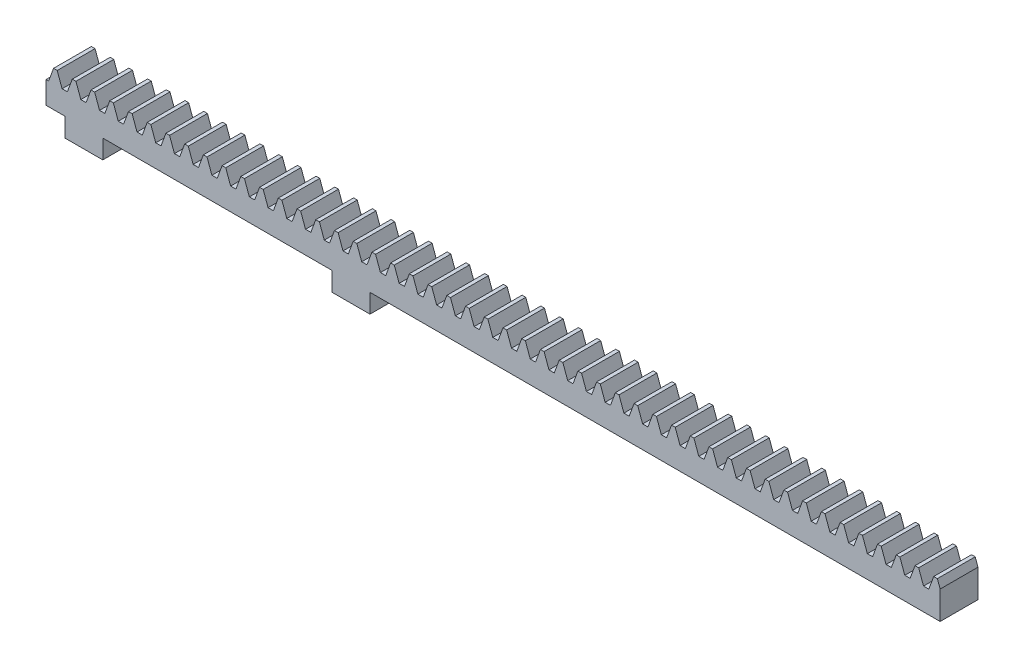
SolidWorks part; units mm, degrees
ref_plane "Plane1" through (0, 0, 0) normal (0, 0, 1) x (1, 0, 0)
ref_plane "Plane2" through (0, 0, 0) normal (0, 1, 0) x (1, 0, 0)
ref_plane "Plane3" through (0, 0, 0) normal (1, 0, 0) x (0, 0, -1)
sketch "HoldingSke" plane through (0, 0, 0) normal (0, 1, 0) x (1, 0, 0)
  line L0 (0, 0) -> (0.1392, 0.9903)
  line L1 (-15, 0) -> (100, 0) construction
  line L2 (0, 0) -> (-2.1039, 2.3779)
  line L3 (0, 0) -> (-11.863, 4.5341)
  line L4 (0, 0) -> (5.6657, 6.5177)
  line L5 (0, 0) -> (-23.7986, -8.8762)
  line L6 (0, 0) -> (-10.5278, -7.1032)
  line L9 (-71.009, 38.7566) -> (69.9449, 90.0596)
  line L10 (-76.2, 3.3779) -> (-71.2, 3.3779)
  line L11 (0, 0) -> (-6.35, 0)
  line L12 (-76.2, 101.6) -> (-76.162, 101.6)
  line L13 (24.9733, 27.94) -> (52.9518, 28.4284)
  line L14 (24.9733, 27.94) -> (24.9743, 27.94)
  line L15 (24.9733, 27.94) -> (100.4006, 29.5858)
  circle A0 centre (0, 0) radius 19.05
  circle A1 centre (0, 0) radius 2.5
  circle A2 centre (0, 0) radius 12.7
  dimension "MPH" = 5
  dimension "Diameter" = 38.1
  dimension "Num_teeth" = 49
  dimension "Pitch" = 1
  dimension "Width" = 6.35
  dimension "Show_teeth" = 998
  dimension "Thickness" = 12.7
  dimension "Ap" = 20
  dimension "Pitch_height" = 5
  dimension "Backlash" = 0.038
  dimension "Addendum_fac" = 1
  dimension "Dedendum_fac" = 1.25
  dimension "Clearance_fac" = 0.25
  dimension "Dedendum_add" = 0.001
  dimension "Length" = 150
  dimension "Module" = 1
sketch "BlankSke" plane through (0, 0, 0) normal (0, 0, 1) x (1, 0, 0)
  line L1 (0, 0) -> (150, 0)
  line L2 (0, 0) -> (0, 6)
  line L3 (0, 6) -> (150, 6)
  line L4 (150, 0) -> (150, 6)
  dimension "Length" = 150
  dimension "Blank_height" = 6
extrude "Blank" add sketch "BlankSke" against normal blind 6.35
sketch "TooCutSkeIll" plane through (0, 0, 0) normal (0, 0, 1) x (1, 0, 0)
  line L0 (-1.2538, 5.9737) -> (-0.5045, 3.9152)
  line L1 (-0.2687, 3.75) -> (0.2687, 3.75)
  line L2 (0.5045, 3.9152) -> (1.2538, 5.9737)
  line L3 (150, 6) -> (0, 6) construction
  line L4 (0, 0) -> (0, 64.897) construction
  line L5 (-13.208, 5) -> (12.954, 5) construction
  line L6 (0, 0) -> (150, 0) construction
  line L7 (0.8994, 5) -> (0.8994, 48.7463) construction
  line L8 (-0.8994, 5) -> (-0.8994, 48.7463) construction
  line L9 (1.2914, 6) -> (1.2914, 6.0254)
  line L10 (-1.2914, 6) -> (-1.2914, 6.0254)
  line L11 (-1.2914, 6.0254) -> (1.2914, 6.0254)
  arc A0 (0.2687, 3.75) -> (0.5045, 3.9152) centre (0.2687, 4.001) ccw
  arc A1 (-0.5045, 3.9152) -> (-0.2687, 3.75) centre (-0.2687, 4.001) ccw
  arc A2 (1.2914, 6) -> (1.2538, 5.9737) centre (1.2914, 5.96) ccw
  arc A3 (-1.2538, 5.9737) -> (-1.2914, 6) centre (-1.2914, 5.96) ccw
  dimension "Root_fillet" = 0.251
  dimension "Break_rad" = 0.04
  dimension "Pitch_height" = 5
  dimension "Gap_width" = 1.7988
  dimension "Dedendum" = 1.25
  dimension "Addendum_plus" = 1.0254
  dimension "Pressure_angle" = 20
extrude "ToothCutIll" [suppressed] cut sketch "TooCutSkeIll" against normal through all
sketch "TooCutSkeSim" plane through (0, 0, 0) normal (0, 0, 1) x (1, 0, 0)
  line L0 (0.4444, 3.75) -> (-0.4444, 3.75)
  line L1 (1.2726, 6.0254) -> (0.4444, 3.75)
  line L2 (0, 17.4625) -> (0, 53.467) construction
  line L3 (1.2726, 6.0254) -> (-1.2726, 6.0254)
  line L6 (-1.2726, 6.0254) -> (-0.4444, 3.75)
  line L9 (-0.8994, 5) -> (0.8994, 5) construction
  line L10 (0, 0) -> (150, 0) construction
  line L11 (0.8994, 5) -> (0.8994, 53.467) construction
  line L12 (-0.8994, 5) -> (-0.8994, 53.467) construction
  dimension "Pitch_height" = 5
  dimension "Pressure_angle" = 20
  dimension "Gap_width" = 1.7988
  dimension "Dedendum" = 1.25
  dimension "Addendum_plus" = 1.0254
extrude "ToothCutSim" cut sketch "TooCutSkeSim" against normal through all
pattern_linear "TeethCuts" count 49 spacing 3.1416 along (1, 0, 0) of "ToothCutIll", "ToothCutSim"
sketch "Sketch1" plane through (0, 0, 0) normal (0, -1, 0) x (1, 0, 0)
  line L0 (48, 0) -> (48, -6.35)
  line L1 (48, 0) -> (54.35, 0)
  line L2 (48, -6.35) -> (54.35, -6.35)
  line L3 (54.35, 0) -> (54.35, -6.35)
  line L6 (0, -6.35) -> (0, 0) construction
  line L7 (0, 0) -> (150, 0) construction
  line L8 (0, -6.35) -> (150, -6.35) construction
  line L9 (3.175, 0) -> (3.175, -6.35)
  line L10 (3.175, 0) -> (9.525, 0)
  line L11 (3.175, -6.35) -> (9.525, -6.35)
  line L12 (9.525, 0) -> (9.525, -6.35)
  dimension "D1" = 48
  dimension "D2" = 6.35
  dimension "D3" = 3.175
  dimension "D4" = 6.35
extrude "ElasticPegs_Extrude" add sketch "Sketch1" along normal blind 3.175
equation "' \"Module@HoldingSke\" = 6.35"
equation "' \"Num_teeth@HoldingSke\" = 12"
equation "' \"Ap@HoldingSke\" =  20"
equation "' \"Width@HoldingSke\" = 0.25 * 25.4"
equation "' \"Show_teeth@HoldingSke\" = 500"
equation "' \"Backlash@HoldingSke\" = 0.009 * 25.4"
equation "' \"Addendum_fac@HoldingSke\" = 1.0"
equation "' \"Dedendum_fac@HoldingSke\" = 1.25"
equation "' \"Dedendum_add@HoldingSke\" = 0.00005 * 25.4"
equation "' \"Clearance_fac@HoldingSke\" = 0.25"
equation "' \"Pitch_height@HoldingSke\" = 1 * 25.4"
equation "' \"Length@HoldingSke\" = 4.71 * 25.4"
equation "\"Pitch@HoldingSke\" = 1 / \"Module@HoldingSke\""
equation "\"MPH@HoldingSke\" = \"Dedendum_fac@HoldingSke\" / \"Pitch@HoldingSke\" + 2 * \"Dedendum_add@HoldingSke\" + 0.002 * 25.4"
equation "\"MPH@HoldingSke\" = ((sgn( \"MPH@HoldingSke\" - \"Pitch_height@HoldingSke\")+1)*( \"MPH@HoldingSke\" - \"Pitch_height@HoldingSke\"))/2 + \"Pitch_height@HoldingSke\""
equation "\"Blank_height@BlankSke\" = \"Pitch_height@HoldingSke\" + \"Addendum_fac@HoldingSke\"  / \"Pitch@HoldingSke\" "
equation "\"Length@BlankSke\" =  \"Length@HoldingSke\""
equation "\"Face_width@Blank\" = \"Width@HoldingSke\""
equation "\"Pressure_angle@TooCutSkeIll\" = \"Ap@HoldingSke\""
equation "\"Addendum_plus@TooCutSkeIll\" =  \"Addendum_fac@HoldingSke\"  / \"Pitch@HoldingSke\" + 0.001 *25.4"
equation "\"Dedendum@TooCutSkeIll\" = \"Dedendum_fac@HoldingSke\"  / \"Pitch@HoldingSke\""
equation "\"Pitch_height@TooCutSkeIll\" =  \"MPH@HoldingSke\""
equation "\"Gap_width@TooCutSkeIll\" = 3.14159265 / 2 / \"Pitch@HoldingSke\" + 6 * \"Backlash@HoldingSke\""
equation "\"Pressure_angle@TooCutSkeSim\" = \"Ap@HoldingSke\""
equation "\"Addendum_plus@TooCutSkeSim\" =  \"Addendum_fac@HoldingSke\"  / \"Pitch@HoldingSke\" + 0.001 * 25.4"
equation "\"Dedendum@TooCutSkeSim\" = \"Dedendum_fac@HoldingSke\"  / \"Pitch@HoldingSke\""
equation "\"Pitch_height@TooCutSkeSim\" =  \"MPH@HoldingSke\""
equation "\"Gap_width@TooCutSkeSim\" = 3.14159265 / 2 / \"Pitch@HoldingSke\" + 6 * \"Backlash@HoldingSke\""
equation "\"Root_fillet@TooCutSkeIll\" = \"Clearance_fac@HoldingSke\" / \"Pitch@HoldingSke\" + \"Dedendum_add@HoldingSke\""
equation "\"Break_rad@TooCutSkeIll\" = 0.02 / \"Pitch@HoldingSke\" * 2"
equation "\"Linear_pitch@TeethCuts\" = 3.14159265 / \"Pitch@HoldingSke\""
equation "\"Num_teeth@HoldingSke\" = int( ( \"Length@HoldingSke\" + 0 ) / (3.14159265 / \"Pitch@HoldingSke\")) + 0.9999  + 1"
equation " \"Num_teeth@TeethCuts\" = int( \"Show_teeth@HoldingSke\" ) + 1"
equation " \"Num_teeth@TeethCuts\" = ((sgn( \"Num_teeth@TeethCuts\" - \"Num_teeth@HoldingSke\" )-1)*( \"Num_teeth@TeethCuts\" - \"Num_teeth@HoldingSke\" ))/-2+ \"Num_teeth@HoldingSke\""
equation " \"Num_teeth@TeethCuts\" = ((sgn( \"Num_teeth@TeethCuts\" - 2.0)+1)*( \"Num_teeth@TeethCuts\" - 2.0))/2 +2.0"
equation "\"CageLeftBottomEdge\"=22.11mm"
equation "\"CageLeftTopEdge\"=22.11mm"
equation "\"CageRightBottomEdge\"=21.63mm"
equation "\"CageRightTopEdge\"=21.63mm"
equation "\"CageHeight\"=86.04mm"
equation "\"CageLength\"=73.76mm"
equation "\"CageTopScrewClearance\"=10mm"
equation "\"CageBottomScrewClearance\"=25mm"
equation "\"CageLeftTopDepth\"= 11.65mm"
equation "\"CageLeftBottomDepth\"=11.11mm"
equation "\"CageLeftTopHeight\"=8.56175mm"
equation "\"CageLeftBottomHeight\"=16mm"
equation "\"CageRightTopDepth\"= 11.05mm"
equation "\"CageRightBottomDepth\"=10.58mm"
equation "\"CageRightTopHeight\"=9.6mm"
equation "\"CageRightBottomHeight\"=15.49mm"
equation "\"CageLeftTopChannelDepth\"=2.41908mm"
equation "\"CageLeftBottomChannelDepth\"=2.588mm"
equation "\"CageLeftChannelHeight\"=11.7mm"
equation "\"CageRightTopChannelDepth\"=2.32mm"
equation "\"CageRightBottomChannelDepth\"=2.318mm"
equation "\"CageRightChannelHeight\"=10mm"
equation "\"CageChanRelHeight\"=23.99mm"
equation "\"CageChanRelDepth\"=5.492mm"
equation "\"CageChamberRadius\"=16.261mm"
equation "\"CageScrewDiameter\"=4.8mm"
equation "\"CageSetScrewDiameter\"=3.5mm"
equation "\"CageAxleRadius\"=6.639mm"
equation "\"CageAxleKeyHeight\"=1.619mm"
equation "\"CageAxleKeyWidth\"=2.662mm"
equation "\"CageHoseWindowWidth\"=16.29mm"
equation "\"CageHoseWindowHeight\"=26.5mm"
equation "\"CageHoseWindow-Edge\"=8.89mm"
equation "\"CageScrew-VerticalEdge\"=5.0mm"
equation "\"CageScrew-HorizontalEdge\"=7.5mm"
equation "\"CageScrew-HoseCornerScrewEdge\"=4.45mm"
equation "\"CageAxle-BottomEdge\"=56.05mm"
equation "\"CageAxle-FrontEdge\"=46.03mm"
equation "\"CageBackSetScrew-Axle\"=40mm"
equation "\"CageFrontSetScrew-Axle\"=22mm"
equation "\"CageVelocityWindow-BackEdge\"=34.8mm"
equation "\"CageVelocityWindow-BottomEdge\"=27.55mm"
equation "\"CageVelocityWindowHeight\"=22.29mm"
equation "\"CageVelocityWindowWidth\"=12.61mm"
equation "\"TriggerSlot-BottomEdge\"=6.35mm"
equation "\"TriggerSlot-FrontEdge\"=15mm"
equation "\"TriggerSlotSize\"=6.7mm"
equation "\"TriggerRackOffset\"=.236224in"
equation "\"TriggerSlotSizeInt\"=.25in"
equation "\"MotorMountLegLength\"=.25in"
equation "\"GearOffset\"=.264907in"
equation "\"TriggerSlotSpacing\"=.25in"
equation "\"TriggerMiniSlotWidth\"=3.5mm"
equation "\"TriggerRackWidth\"=6.5mm"
equation "\"TGMGearFaceDiameter\"=24.40mm"
equation "\"TGMCylinderLength\"=15.00mm"
equation "\"TGMScrewHole-Center\"=8.70mm"
equation "\"TGMScrewHoleDiameter\"=5.04mm"
equation "\"TGMCenterHoleDiameter\"=9.50mm"
equation "\"TGMShaftCollarSideLength\"=19.00mm"
equation "\"TGMShaftCollarDockingDepth\"=7.00mm"
equation "\"whitemotordepth\"=11.27mm"
equation "\"whitemotorbackdepth\"=3.845mm"
equation "\"whitemotoraxledepth\" = 3.5mm"
equation "\"whitemotoraxleoffset\"=11.4mm"
equation "\"whitemotorwidth\"=12.07mm"
equation "\"whitemotorheight\"=16.68mm"
equation "\"whitemotorcylinderlength\" =13.04mm"
equation "\"whitemotorcylinderradius\"=3.845mm"
equation "\"whitemotorcylinderoffset\"=2.35mm"
equation "\"whitemotorcutoutlength\"=1.88mm"
equation "\"whitemotorouterrad\"=5mm"
equation "\"whitemotorinnerrad\"=2.95mm"
equation "\"elasticracklength\"=2in"
equation "\"elasticrackpegsize\"=.25in"
equation "\"elasticrackpegbuffer\"=.125in"
equation "\"elasticrackpegspacing\"=1.76476378in"
equation "\"elasticbaybuffer\"=.25in"
equation "\"elasticdepth\"=.125in"
equation "\"elasticbaydepth\"=.75in"
equation "\"motormountwidth\"=12mm"
equation "\"motormountcornerfillet\"=3mm"
equation "\"D2@Sketch1\"=\"elasticrackpegsize\""
equation "\"D4@Sketch1\"=\"elasticrackpegsize\""
equation "\"D3@Sketch1\"=\"elasticrackpegsize\"/2"
equation "\"D1@Sketch1\"=\"elasticrackpegspacing\"+\"elasticrackpegsize\"/2"
equation "\"pandiscradius\"=14in"
equation "\"towermaterialwidth\"=.25in"
equation "\"towerslotlength\"=.5in"
equation "\"towermarkerspace\"=5in"
equation "\"towerslothorizoffset\"=1in"
equation "\"towerslothorizspacing\"=2in"
equation "\"towerslotvertoffset\"=3in"
equation "\"towerslotvertspacing\"=2in"
equation "\"towerheight\"=12in"
equation "\"towerupslot\"=1in"
equation "\"toweraxle\"=.5in"
equation "\"towerplatslotoffset\"=1.5in"
equation "\"towermotorpanelheight\"=10in"
equation "\"towerplatdepth\"=2in"
equation "\"stepperouterrad\"=10mm"
equation "\"stepperscrewsize\"=3.45mm"
equation "\"stepperscrewc2c\"=49.5mm"
equation "\"stepperdepthoffset\"=24mm"
equation "\"stepperhorizoffset\"=22.91mm"
equation "\"shaftslotOD\"=18.8mm"
equation "\"shaftslotID\"=13.28mm"
equation "\"shaftkeywidth\"=2.67mm"
equation "\"shaftkeydepth\"=1.8mm"
equation "\"shaftcollartotaldepth\"=12.5mm"
equation "\"shaftsquaredepth\"=6mm"
equation "\"shaftsetscrewsize\"=3.5mm"
equation "\"shaftkeytightdepth\"=1.85mm"
equation "\"shaftslottightID\"=12.78mm"
equation "\"shaftsetscrewoffset\"=9mm"
equation "\"cagecollartotaldepth\"=10mm"
equation "\"cagecollartotalwidth\"=35mm"
equation "\"cagecollarbasedepth\"=4mm"
